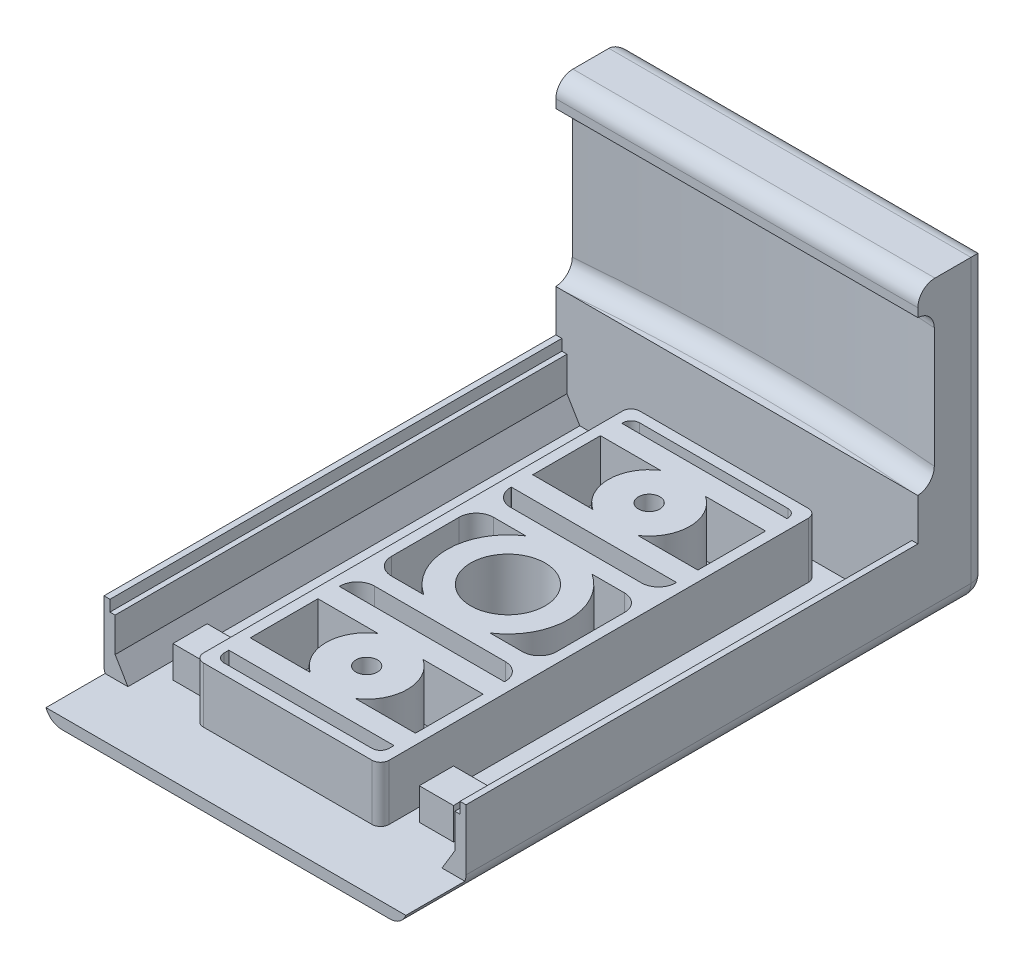
SolidWorks part; units mm, degrees
ref_plane "Alzado" through (0, 0, 0) normal (0, 0, 1) x (1, 0, 0)
ref_plane "Planta" through (0, 0, 0) normal (0, 1, 0) x (1, 0, 0)
ref_plane "Vista lateral" through (0, 0, 0) normal (1, 0, 0) x (0, 0, -1)
sketch "Croquis1" plane through (0, 0, 0) normal (1, 0, 0) x (0, 0, -1)
  line L1 (-38.1383, -2.2273) -> (21.5617, -2.2273)
  line L2 (-38.1383, -2.2273) -> (-38.1383, -11.3273)
  line L3 (-38.1383, -11.3273) -> (29.7617, -11.3273)
  line L4 (29.7617, -2.2617) -> (29.7617, -11.3273)
  line L6 (29.7617, -2.2617) -> (29.7617, 23.6727)
  line L7 (29.7617, 23.6727) -> (21.5617, 23.6727)
  line L8 (21.5617, -2.2273) -> (21.5617, 23.6727)
  dimension "D1" = 67.9
  dimension "D2" = 9.1
  dimension "D3" = 8.2
  dimension "D4" = 59.7
  dimension "D5" = 35
extrude "Saliente-Extruir1" add sketch "Croquis1" against normal blind 42.3
sketch "Croquis3" plane through (0, -2.2273, 0) normal (0, 1, 0) x (1, 0, 0)
  line L0 (0, 21.5617) -> (0, -38.1383) construction
  line L1 (-41.6, 21.5617) -> (-0.7, 21.5617)
  line L2 (-41.6, 21.5617) -> (-41.6, -35.3383)
  line L3 (-41.6, -35.3383) -> (-0.7, -35.3383)
  line L4 (-0.7, 21.5617) -> (-0.7, -35.3383)
  line L5 (-42.3, 21.5617) -> (-42.3, -38.1383) construction
  line L6 (-42.3, 21.5617) -> (0, 21.5617) construction
  dimension "D1" = 0.7
  dimension "D2" = 0.7
  dimension "D3" = 56.9
extrude "Cortar-Extruir1" cut sketch "Croquis3" against normal blind 1.3
sketch "Croquis5" plane through (0, -2.2273, 0) normal (0, 1, 0) x (1, 0, 0)
  line L0 (0, 21.5617) -> (0, -38.1383) construction
  line L1 (-42.3, -38.1383) -> (0, -38.1383)
  line L2 (-42.3, -38.1383) -> (-42.3, -35.3383)
  line L3 (-42.3, -35.3383) -> (0, -35.3383)
  line L4 (0, -38.1383) -> (0, -35.3383)
  line L5 (-41.6, -35.3383) -> (-0.7, -35.3383) construction
extrude "Cortar-Extruir2" cut sketch "Croquis5" against normal blind 7.8
sketch "Croquis6" plane through (0, 0, -21.5617) normal (0, 0, 1) x (1, 0, 0)
  line L0 (-41.6, -3.5273) -> (-0.7, -3.5273) construction
  line L1 (-41.6, 22.9727) -> (-0.7, 22.9727)
  line L2 (-41.6, 22.9727) -> (-41.6, -3.5273)
  line L3 (-41.6, -3.5273) -> (-0.7, -3.5273)
  line L4 (-0.7, 22.9727) -> (-0.7, -3.5273)
  line L5 (0, 23.6727) -> (0, -2.2273) construction
  line L6 (-42.3, 23.6727) -> (0, 23.6727) construction
  line L7 (-42.3, 23.6727) -> (-42.3, -2.2273) construction
  dimension "D1" = 0.7
  dimension "D2" = 0.7
  dimension "D3" = 0.7
extrude "Cortar-Extruir3" cut sketch "Croquis6" against normal blind 1.3
sketch "Croquis8" plane through (0, -3.5273, 0) normal (0, 1, 0) x (1, 0, 0)
  line L0 (0, 21.5617) -> (0, -35.3383) construction
  line L1 (-41, 21.5617) -> (-1.3, 21.5617)
  line L2 (-41, 21.5617) -> (-41, -35.3383)
  line L3 (-41, -35.3383) -> (-1.3, -35.3383)
  line L4 (-1.3, 21.5617) -> (-1.3, -35.3383)
  line L6 (-42.3, 21.5617) -> (-42.3, -35.3383) construction
  line L7 (0, -35.3383) -> (-42.3, -35.3383) construction
  line L8 (-42.3, 21.5617) -> (0, 21.5617) construction
  dimension "D1" = 1.3
  dimension "D2" = 1.3
extrude "Cortar-Extruir4" cut sketch "Croquis8" against normal up to surface (6.5 mm away) up to face at (-21.15, -10.0273, 36.7383)
sketch "Croquis9" plane through (0, 0, -21.5617) normal (0, 0, 1) x (1, 0, 0)
  line L0 (-41, -10.0273) -> (-41, -3.5273) construction
  line L1 (-1.3, -10.0273) -> (-41, -10.0273)
  line L2 (-1.3, -10.0273) -> (-1.3, 22.1727)
  line L3 (-1.3, 22.1727) -> (-41, 22.1727)
  line L4 (-41, -10.0273) -> (-41, 22.1727)
  line L5 (-42.3, 23.6727) -> (0, 23.6727) construction
  dimension "D1" = 1.5
extrude "Cortar-Extruir5" cut sketch "Croquis9" against normal blind 7.3
sketch "Croquis10" plane through (0, -10.0273, 0) normal (0, 1, 0) x (1, 0, 0)
  line L1 (-32, 20.0617) -> (-10.3, 20.0617)
  line L2 (-32, 20.0617) -> (-32, -30.9175)
  line L3 (-32, -30.9175) -> (-10.3, -30.9175)
  line L4 (-10.3, 20.0617) -> (-10.3, -30.9175)
  line L5 (-30.8, 18.8617) -> (-11.5, 18.8617)
  line L6 (-30.8, 18.8617) -> (-30.8, -29.7175)
  line L7 (-30.8, -29.7175) -> (-11.5, -29.7175)
  line L8 (-11.5, 18.8617) -> (-11.5, -29.7175)
  line L11 (-42.3, 21.5617) -> (0, 21.5617) construction
  line L12 (-41, 28.8617) -> (-41, -35.3383) construction
  line L13 (-1.3, -35.3383) -> (-1.3, 28.8617) construction
  dimension "D1" = 9
  dimension "D2" = 9
  dimension "D3" = 1.5
  dimension "D4" = 1.2
  dimension "D5" = 1.2
  dimension "D6" = 1.2
  dimension "D7" = 1.2
extrude "Saliente-Extruir2" add sketch "Croquis10" along normal up to surface (6.5 mm away) up to face at (-1, -3.5273, 6.2383)
fillet "Redondeo6" radius 1 4 edges at (-11.5, -6.7773, 29.7175) (-30.8, -6.7773, 29.7175) (-11.5, -6.7773, -18.8617) (-30.8, -6.7773, -18.8617)
fillet "Redondeo7" radius 1 4 edges at (-32, -6.7773, -20.0617) (-32, -6.7773, 30.9175) (-10.3, -6.7773, -20.0617) (-10.3, -6.7773, 30.9175)
sketch "Croquis17" plane through (0, 0, -28.8617) normal (0, 0, 1) x (1, 0, 0)
  line L1 (-41, 22.1727) -> (-1.3, 22.1727)
  line L2 (-41, 22.1727) -> (-41, -10.0273)
  line L3 (-41, -10.0273) -> (-1.3, -10.0273)
  line L4 (-1.3, 22.1727) -> (-1.3, -10.0273)
extrude "Saliente-Extruir4" add sketch "Croquis17" along normal up to surface (6 mm away) up to face at (-21.15, 9.5227, -22.8617)
sketch "Croquis18" plane through (0, 0, -22.8617) normal (0, 0, 1) x (1, 0, 0)
  line L0 (-41.6, 22.9727) -> (-41.6, -3.5273)
  line L1 (-41.6, -3.5273) -> (-41, -3.5273)
  line L2 (-41, -3.5273) -> (-41, -10.0273)
  line L3 (-41, -10.0273) -> (-1.3, -10.0273)
  line L4 (-1.3, -10.0273) -> (-1.3, -3.5273)
  line L5 (-1.3, -3.5273) -> (-0.7, -3.5273)
  line L6 (-0.7, -3.5273) -> (-0.7, 22.9727)
  line L7 (-0.7, 22.9727) -> (-41.6, 22.9727)
extrude "Saliente-Extruir5" add sketch "Croquis18" along normal up to surface (1.3 mm away) up to face at (-21.15, 10.5477, -21.5617)
sketch "Croquis19" plane through (0, 23.6727, 0) normal (0, 1, 0) x (1, 0, 0)
  line L0 (-42.3, 23.4817) -> (0, 23.4817) construction
  line L1 (-42.3, 29.7617) -> (-42.3, 21.5617) construction
  line L2 (0, 29.7617) -> (0, 21.5617) construction
  line L3 (-42.3, 23.4817) -> (-42.3, 21.5617)
  line L4 (-42.3, 21.5617) -> (0, 21.5617)
  line L5 (0, 21.5617) -> (0, 23.4817)
  arc A0 (-42.3, 23.4817) -> (0, 23.4817) centre (-21.15, -215.5845) cw
  dimension "D2" = 240
  dimension "D1" = 1.92
sketch "Croquis21" plane through (0, 23.6727, 0) normal (0, 1, 0) x (1, 0, 0)
sketch "Croquis22" plane through (0, 23.6727, 0) normal (0, 1, 0) x (1, 0, 0)
extrude "Cortar-Extruir6" cut sketch "Croquis19" against normal blind 21
fillet "Redondeo8" radius 2 4 edges at (-21.15, -11.3273, -29.7617) (-42.3, 6.1727, -29.7617) (0, 6.1727, -29.7617) (-21.15, 23.6727, -29.7617)
sketch "Croquis23" plane through (0, -10.0273, 0) normal (0, 1, 0) x (1, 0, 0)
  line L0 (-21.15, 21.5617) -> (-21.15, -38.1383) construction
  line L1 (-41, 21.5617) -> (-1.3, 21.5617) construction
  line L2 (-42.3, -38.1383) -> (0, -38.1383) construction
  line L3 (-42.3, -35.3383) -> (0, -35.3383) construction
  line L4 (-4.76, -27.9383) -> (-8.76, -27.9383)
  line L5 (-37.54, -23.9383) -> (-33.54, -23.9383)
  line L6 (-37.54, -23.9383) -> (-37.54, -27.9383)
  line L7 (-37.54, -27.9383) -> (-33.54, -27.9383)
  line L8 (-33.54, -23.9383) -> (-33.54, -27.9383)
  line L9 (-8.76, -23.9383) -> (-8.76, -27.9383)
  line L10 (-4.76, -23.9383) -> (-8.76, -23.9383)
  line L11 (-4.76, -23.9383) -> (-4.76, -27.9383)
  line L12 (-32, 19.0617) -> (-32, -29.9175) construction
  dimension "D1" = 4
  dimension "D2" = 4
  dimension "D3" = 1.54
  dimension "D4" = 7.4
fillet "Redondeo10" radius 2 4 edges at (-41.7142, -10.7416, -29.176) (-0.5858, -10.7416, -29.176) (-42.3, -11.3273, 5.1883) (0, -11.3273, 5.1883)
sketch "Croquis26" plane through (0, -10.0273, 0) normal (0, 1, 0) x (1, 0, 0)
  line L0 (-21.15, -38.1383) -> (-21.15, 27.7617) construction
  line L1 (-42.1735, -38.1383) -> (-0.1265, -38.1383) construction
  line L2 (0, 27.7617) -> (-42.3, 27.7617) construction
  line L3 (-42.3, -3.1883) -> (0, -3.1883) construction
  line L4 (-42.3, 21.5617) -> (-42.3, -35.3383) construction
  line L5 (0, 21.5617) -> (0, -35.3383) construction
  circle A0 centre (-21.15, -5.1883) radius 7.1
  circle A1 centre (-21.15, -5.1883) radius 4.35
  dimension "D2" = 8.7
  dimension "D3" = 14.2
  dimension "D1" = 34.95
extrude "Saliente-Extruir7" add sketch "Croquis26" along normal up to surface (6.5 mm away) up to face at (-21.15, -3.5273, 5.4279)
sketch "Croquis27" plane through (0, -10.0273, 0) normal (0, 1, 0) x (1, 0, 0)
  circle A0 centre (-21.15, -5.1883) radius 4.35
  dimension "D1" = 8.7
extrude "Cortar-Extruir7" cut sketch "Croquis27" against normal blind 44
sketch "Croquis28" plane through (0, -10.0273, 0) normal (0, 1, 0) x (1, 0, 0)
  line L0 (-30.8, 17.8617) -> (-30.8, -28.7175) construction
  line L1 (-30.8, 2.7691) -> (-11.5, 2.7691)
  line L2 (-30.8, 2.7691) -> (-30.8, 0.7691)
  line L3 (-30.8, 0.7691) -> (-11.5, 0.7691)
  line L4 (-11.5, 2.7691) -> (-11.5, 0.7691)
  line L5 (-11.5, -28.7175) -> (-11.5, 17.8617) construction
  line L6 (-21.15, -5.1883) -> (-11.5, -5.1883) construction
  line L7 (-11.5, -28.7175) -> (-11.5, 17.8617) construction
  line L8 (-30.8, -11.1456) -> (-11.5, -11.1456)
  line L9 (-11.5, -13.1456) -> (-11.5, -11.1456)
  line L10 (-30.8, -13.1456) -> (-11.5, -13.1456)
  line L11 (-30.8, -13.1456) -> (-30.8, -11.1456)
  dimension "D1" = 19.3
  dimension "D2" = 2
extrude "Saliente-Extruir8" add sketch "Croquis28" along normal up to surface (6.5 mm away) up to face at (-21.15, -3.5273, 9.5383)
fillet "Redondeo11" radius 2 4 edges at (-30.8, -6.7773, 11.1456) (-11.5, -6.7773, 11.1456) (-30.8, -6.7773, -0.7691) (-11.5, -6.7773, -0.7691)
fillet "Redondeo12" radius 2 4 edges at (-30.8, -6.7773, -2.7691) (-11.5, -6.7773, -2.7691) (-30.8, -6.7773, 13.1456) (-11.5, -6.7773, 13.1456)
sketch "Croquis30" plane through (0, -10.0273, 0) normal (0, 1, 0) x (1, 0, 0)
  line L0 (-21.15, 18.8617) -> (-21.15, -29.7175) construction
  line L1 (-12.5, 18.8617) -> (-29.8, 18.8617) construction
  line L2 (-29.8, -29.7175) -> (-12.5, -29.7175) construction
  line L3 (-30.8, 11.3154) -> (-11.5, 11.3154) construction
  line L4 (-30.8, 17.8617) -> (-30.8, 4.7691) construction
  line L5 (-11.5, 4.7691) -> (-11.5, 17.8617) construction
  line L6 (-25.5, -5.1883) -> (-16.8, -5.1883) construction
  circle A0 centre (-21.15, 11.3154) radius 1.25
  circle A1 centre (-21.15, 11.3154) radius 4.75
  circle A2 centre (-21.15, -5.1883) radius 4.35 construction
  circle A3 centre (-21.15, -21.6919) radius 1.25
  circle A4 centre (-21.15, -21.6919) radius 4.75
  dimension "D1" = 2.5
  dimension "D2" = 3.5
extrude "Saliente-Extruir9" add sketch "Croquis30" along normal up to surface (6.5 mm away) up to face at (-13.4182, -3.5273, 5.1883)
sketch "Croquis33" plane through (0, -10.0273, 0) normal (0, 1, 0) x (1, 0, 0)
  line L0 (-30.8, 17.8617) -> (-30.8, 4.7691) construction
  line L1 (-30.8, 17.7699) -> (-11.5, 17.7699)
  line L2 (-30.8, 17.7699) -> (-30.8, 15.2699)
  line L3 (-30.8, 15.2699) -> (-11.5, 15.2699)
  line L4 (-11.5, 17.7699) -> (-11.5, 15.2699)
  line L5 (-11.5, 4.7691) -> (-11.5, 17.8617) construction
  line L6 (-22.4, 11.3154) -> (-19.9, 11.3154) construction
  line L7 (-30.8, 7.3609) -> (-11.5, 7.3609)
  line L8 (-11.5, 4.8609) -> (-11.5, 7.3609)
  line L9 (-30.8, 4.8609) -> (-11.5, 4.8609)
  line L10 (-30.8, 4.8609) -> (-30.8, 7.3609)
  line L11 (-25.5, -5.1883) -> (-16.8, -5.1883) construction
  line L12 (-30.8, -15.2374) -> (-30.8, -17.7374)
  line L13 (-30.8, -15.2374) -> (-11.5, -15.2374)
  line L14 (-11.5, -15.2374) -> (-11.5, -17.7374)
  line L15 (-30.8, -17.7374) -> (-11.5, -17.7374)
  line L16 (-30.8, -25.6465) -> (-11.5, -25.6465)
  line L17 (-11.5, -28.1465) -> (-11.5, -25.6465)
  line L18 (-30.8, -28.1465) -> (-11.5, -28.1465)
  line L19 (-30.8, -28.1465) -> (-30.8, -25.6465)
  circle A0 centre (-21.15, 11.3154) radius 1.25 construction
  circle A1 centre (-21.15, 11.3154) radius 1.25 construction
  circle A2 centre (-21.15, -5.1883) radius 4.35 construction
  dimension "D1" = 2.5
  dimension "D2" = 19.3
extrude "Saliente-Extruir11" add sketch "Croquis33" along normal up to surface (6.5 mm away) up to face at (-13.4182, -3.5273, 5.1883)
sketch "Croquis34" plane through (0, 0, 35.3383) normal (0, 0, 1) x (1, 0, 0)
  line L0 (-1.3, -10.0273) -> (-1.3, -3.5273)
  line L1 (-1.3, -3.5273) -> (-0.7, -3.5273)
  line L2 (-0.7, -3.5273) -> (-0.7, -2.2273)
  line L3 (-0.7, -2.2273) -> (0, -2.2273)
  line L4 (0, -2.2273) -> (0, -10.0273)
  line L5 (-42.3, -10.0273) -> (0, -10.0273) construction
  line L6 (0, -10.0273) -> (-1.3, -10.0273)
  line L7 (-21.15, -11.3273) -> (-21.15, -3.5273) construction
  line L8 (-40.3, -11.3273) -> (-2, -11.3273) construction
  line L9 (-31, -3.5273) -> (-11.3, -3.5273) construction
  line L10 (-42.3, -2.2273) -> (-42.3, -10.0273)
  line L11 (-41.6, -2.2273) -> (-42.3, -2.2273)
  line L12 (-41.6, -3.5273) -> (-41.6, -2.2273)
  line L13 (-41, -3.5273) -> (-41.6, -3.5273)
  line L14 (-41, -10.0273) -> (-41, -3.5273)
  line L15 (-42.3, -10.0273) -> (-41, -10.0273)
extrude "Cortar-Extruir8" cut sketch "Croquis34" against normal blind 4.1 contours L10 L15 L14 L13 L12 L11 | L6 L0 L1 L2 L3 L4
extrude "Saliente-Extruir12" add sketch "Croquis23" along normal blind 3.7
ref_plane "Plano1" through (0, 0, 4.8383) normal (0, 0, 1) x (1, 0, 0)
sketch "Croquis39" plane through (0, 0, 4.8383) normal (0, 0, 1) x (1, 0, 0)
  line L0 (-41, -7.5273) -> (-39.5, -10.0273)
  line L1 (-41, -3.5273) -> (-41, -10.0273) construction
  line L2 (-42.1735, -10.0273) -> (-0.1265, -10.0273) construction
  dimension "D1" = 2.5
  dimension "D2" = 1.5
rib "Nervio5" sketch "Croquis39" sketch "Croquis39" thickness 52.8 extrusion direction parallel to sketch draft on no parameters "D1"=52.8
ref_plane "Plano2" through (0, 0, 4.8383) normal (0, 0, 1) x (1, 0, 0)
sketch "Croquis43" plane through (0, 0, 4.8383) normal (0, 0, 1) x (1, 0, 0)
  line L0 (-1.3, -7.5273) -> (-2.8, -10.0273)
  line L1 (-1.3, -10.0273) -> (-1.3, -3.5273) construction
  line L2 (-39.5, -10.0273) -> (-1.3, -10.0273) construction
  line L3 (-1.3, -10.0273) -> (-1.3, -3.5273) construction
  dimension "D1" = 2.5
  dimension "D2" = 1.5
rib "Nervio7" sketch "Croquis43" sketch "Croquis43" thickness 52.8 extrusion direction parallel to sketch draft on no parameters "D1"=52.8
sketch "Croquis44" plane through (0, 0, -21.5617) normal (0, 0, 1) x (1, 0, 0)
  line L0 (0, 2.6727) -> (0, 23.6727) construction
  line L1 (-42.3, 23.6727) -> (0, 23.6727)
  line L2 (-42.3, 23.6727) -> (-42.3, 20.6727)
  line L3 (-42.3, 20.6727) -> (0, 20.6727)
  line L4 (0, 23.6727) -> (0, 20.6727)
  dimension "D1" = 3
extrude "Saliente-Extruir13" add sketch "Croquis44" against normal blind 4.7
fillet "Redondeo13" radius 2 2 edges at (-21.15, 2.6727, -24.4155) (-21.15, 20.6727, -24.4155)
fillet "Redondeo14" radius 2 1 edges at (-21.15, 23.6727, -21.5617)
